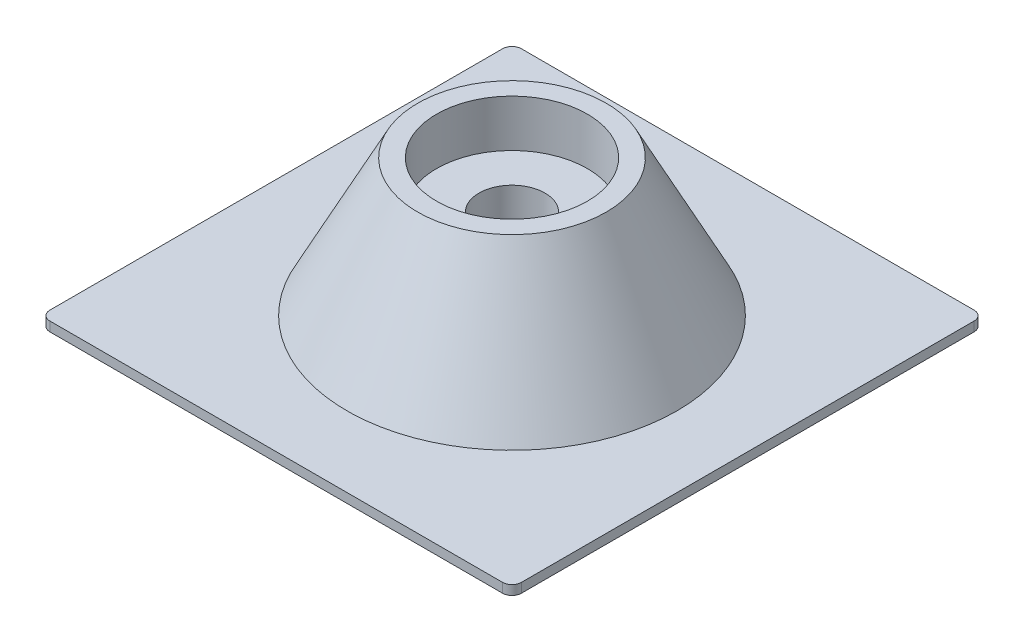
SolidWorks part; units mm, degrees
ref_plane "Front Plane" through (0, 0, 0) normal (0, 0, 1) x (1, 0, 0)
ref_plane "Top Plane" through (0, 0, 0) normal (0, 1, 0) x (1, 0, 0)
ref_plane "Right Plane" through (0, 0, 0) normal (1, 0, 0) x (0, 0, -1)
sketch "Sketch1" plane through (0, 0, 0) normal (0, 1, 0) x (1, 0, 0)
  line L0 (-25, 25) -> (25, -25) construction
  line L1 (-24, 25) -> (24, 25)
  line L2 (-25, 24) -> (-25, -24)
  line L3 (-24, -25) -> (24, -25)
  line L4 (25, 24) -> (25, -24)
  arc A0 (24, 25) -> (25, 24) centre (24, 24) cw
  arc A1 (-25, -24) -> (-24, -25) centre (-24, -24) ccw
  arc A2 (24, -25) -> (25, -24) centre (24, -24) ccw
  arc A3 (-24, 25) -> (-25, 24) centre (-24, 24) ccw
  circle A4 centre (0, 0) radius 3.5
  point P7 (25, 25)
  dimension "D2" = 1
  dimension "D3" = 7
  dimension "D1" = 50
extrude "Boss-Extrude1" add sketch "Sketch1" along normal blind 0.5 and the other way blind 0.5
sketch "Sketch2" plane through (0, 0, 0) normal (0, 0, 1) x (1, 0, 0)
  line L0 (0, 0.5) -> (0, 15) construction
  line L1 (-24, 0.5) -> (24, 0.5) construction
  line L2 (-8, 15) -> (-10, 15)
  line L3 (-10, 15) -> (-17.5, 0.5)
  line L4 (-8, 15) -> (-8, 10)
  line L5 (-8, 10) -> (-3.5, 10)
  line L6 (-3.5, 10) -> (-3.5, 0.5)
  line L7 (-3.5, 0.5) -> (-17.5, 0.5)
  dimension "D1" = 14.5
  dimension "D2" = 10
  dimension "D3" = 7.5
  dimension "D4" = 2
  dimension "D5" = 5
  dimension "D6" = 4.5
revolve "Revolve1" add sketch "Sketch2" angle 360 about L0
